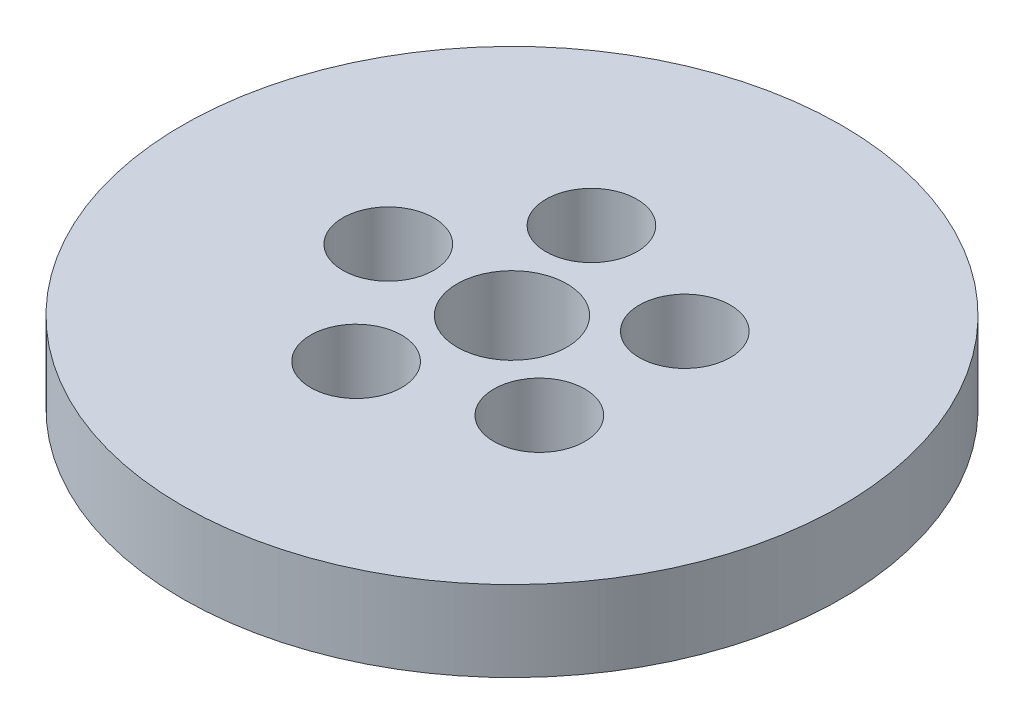
SolidWorks part; units mm, degrees
ref_plane "Front Plane" through (0, 0, 0) normal (0, 0, 1) x (1, 0, 0)
ref_plane "Top Plane" through (0, 0, 0) normal (0, 1, 0) x (1, 0, 0)
ref_plane "Right Plane" through (0, 0, 0) normal (1, 0, 0) x (0, 0, -1)
sketch "Sketch1" plane through (0, 0, 0) normal (0, 1, 0) x (1, 0, 0)
  circle A0 centre (0, 0) radius 45
  dimension "FLANGE_OD" = 90
extrude "Boss-Extrude1" add sketch "Sketch1" along normal blind 11
sketch "Sketch2" plane through (0, 0, 0) normal (0, 1, 0) x (1, 0, 0)
  circle A0 centre (0, 0) radius 7.5
  dimension "BORE_D" = 15
extrude "Cut-Extrude1" cut sketch "Sketch2" along normal through all
sketch "Sketch3" plane through (0, 11, 0) normal (0, 1, 0) x (1, 0, 0)
  circle A0 centre (0, 0) radius 16.8926 construction
  circle A1 centre (-16.8926, 0) radius 6.2177
  dimension "BOLT_D" = 12.4353
  dimension "BOLT_PCD" = 33.7852
extrude "Cut-Extrude2" cut sketch "Sketch3" against normal blind 10.6021
pattern_circular "CirPattern1" count 5 over 360 about axis through (0, 0, 0) along (0, 1, 0) of "Cut-Extrude2"
